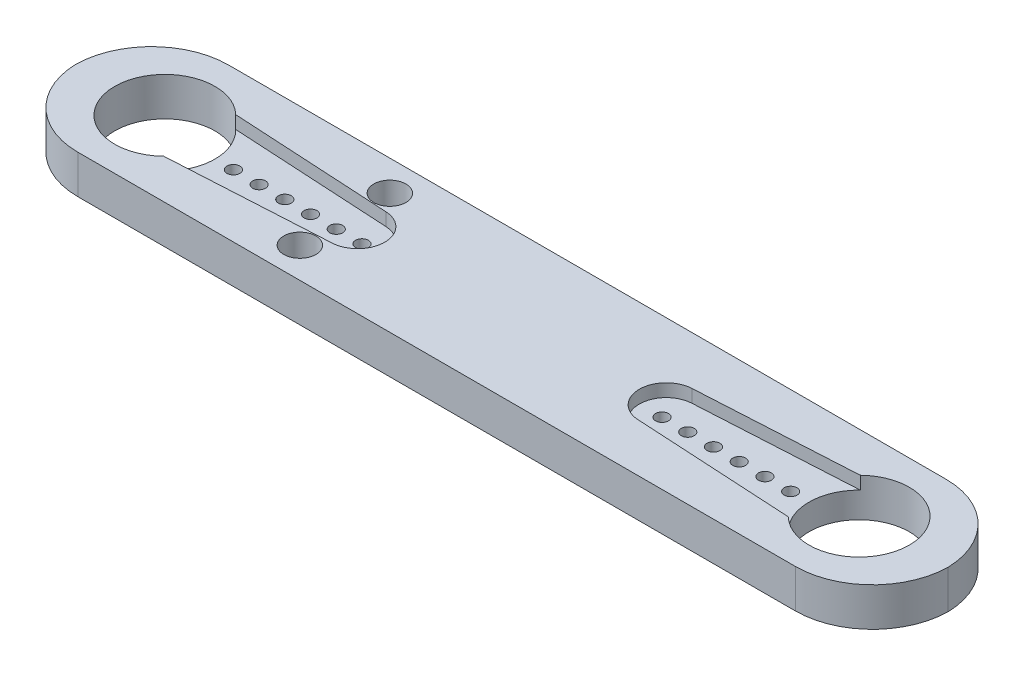
SolidWorks part; units mm, degrees
material "ABS"
ref_plane "Front" through (0, 0, 0) normal (0, 0, 1) x (1, 0, 0)
ref_plane "Top" through (0, 0, 0) normal (0, 1, 0) x (1, 0, 0)
ref_plane "Right" through (0, 0, 0) normal (1, 0, 0) x (0, 0, -1)
sketch "Sketch1" plane through (0, 0, 0) normal (0, 1, 0) x (1, 0, 0)
  line L0 (-15.948, 2.8) -> (-3.5476, 2.1)
  line L1 (-18.6628, 0) -> (-3.5476, 0) construction
  line L2 (-3.5476, -2.1) -> (-15.948, -2.8)
  line L3 (-22.5628, 0) -> (0, 0) construction
  line L4 (-15.948, 2.8) -> (-15.948, -2.8) construction
  line L5 (8.3372, 5.8662) -> (8.3372, -5.8662) construction
  line L6 (-25.5628, 5.8662) -> (42.2372, 5.8662)
  line L7 (-25.5628, 5.8662) -> (-25.5628, -5.8662)
  line L8 (-25.5628, -5.8662) -> (42.2372, -5.8662)
  line L9 (42.2372, 5.8662) -> (42.2372, -5.8662)
  line L10 (32.6224, 2.8) -> (32.6224, -2.8) construction
  line L11 (39.2372, 0) -> (16.6744, 0) construction
  line L12 (35.3372, 0) -> (20.222, 0) construction
  line L13 (20.222, -2.1) -> (32.6224, -2.8)
  line L14 (32.6224, 2.8) -> (20.222, 2.1)
  line L15 (8.3372, 0) -> (5.1075, 0) construction
  circle A0 centre (-18.6628, 0) radius 3.9
  arc A1 (-3.5476, 2.1) -> (-3.5476, -2.1) centre (-3.6662, 0) cw
  circle A2 centre (-3.3314, 0) radius 0.5
  circle A3 centre (-5.3314, 0) radius 0.5
  circle A4 centre (-7.3314, 0) radius 0.5
  circle A5 centre (-9.3314, 0) radius 0.5
  circle A6 centre (-11.3314, 0) radius 0.5
  circle A7 centre (-13.3314, 0) radius 0.5
  circle A8 centre (-18.6628, 0) radius 2.4
  circle A9 centre (-18.6628, 0) radius 1.6
  circle A10 centre (35.3372, 0) radius 1.6
  circle A11 centre (35.3372, 0) radius 2.4
  circle A12 centre (30.0058, 0) radius 0.5
  circle A13 centre (28.0058, 0) radius 0.5
  circle A14 centre (26.0058, 0) radius 0.5
  circle A15 centre (24.0058, 0) radius 0.5
  circle A16 centre (22.0058, 0) radius 0.5
  circle A17 centre (20.0058, 0) radius 0.5
  arc A18 (20.222, 2.1) -> (20.222, -2.1) centre (20.3405, 0) ccw
  circle A19 centre (35.3372, 0) radius 3.9
  circle A20 centre (-4.6628, 3.5) radius 1.25
  circle A21 centre (-4.6628, -3.5) radius 1.25
  point P13 (-1.5628, 0)
  point P57 (18.2372, 0)
  dimension "D1" = 7.8
  dimension "D2" = 54
  dimension "D5" = 1
  dimension "D7" = 4.8
  dimension "D8" = 3.2
  dimension "D11" = 7
  dimension "D10" = 2.5
  dimension "D3" = 5.6
  dimension "D6" = 21
  dimension "D9" = 3
  dimension "D12" = 13
  dimension "D4" = 6
extrude "Boss-Extrude1" add sketch "Sketch1" along normal blind 3 contours L9 L6 L7 L8 L0 A1 L2 A0 | L9 | L9 region at (8.5632, 0, 0)
extrude "Boss-Extrude2" add sketch "Sketch1<7>" along normal blind 2 contours A1 L0 A0 L2 A7 A6 A5 A4 A3 A2 | L13 A19 L14 A18 A17 A15 A13 A12 A14 A16 region at (-9.7565, 0, -2.2959) region at (18.3916, 0, 0)
sketch "Sketch1<7>" plane through (0, 0, 0) normal (0, 1, 0) x (1, 0, 0) same geometry as "Sketch1"
fillet "Fillet1" radius 6 4 edges at (-25.5628, 1.5, 5.8662) (-25.5628, 1.5, -5.8662) (42.2372, 1.5, -5.8662) (42.2372, 1.5, 5.8662)
